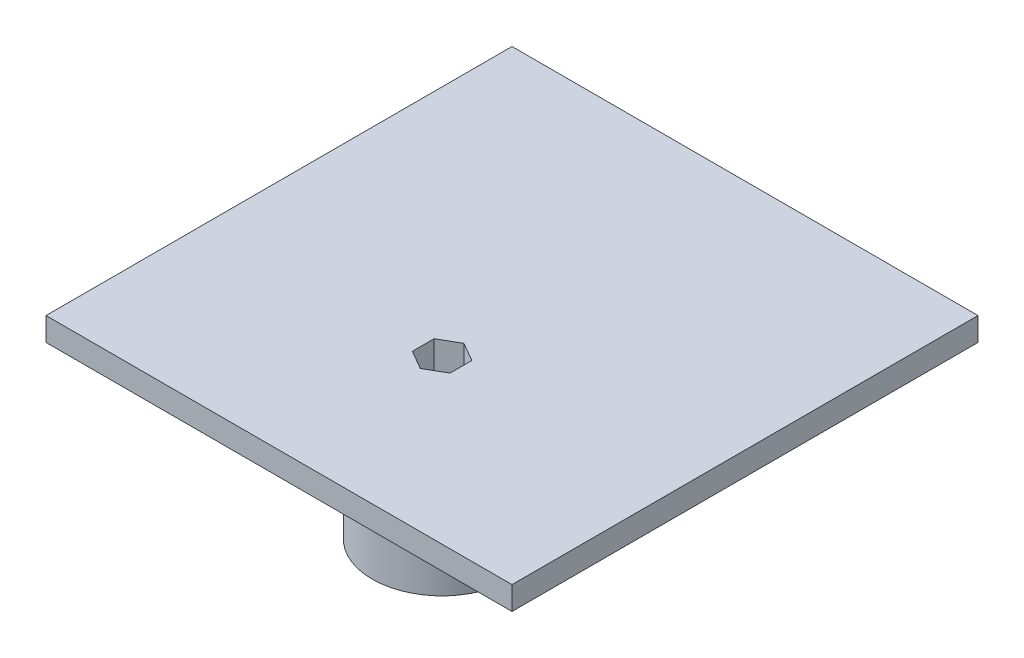
SolidWorks part; units mm, degrees
ref_plane "Plan de face" through (0, 0, 0) normal (0, 0, 1) x (1, 0, 0)
ref_plane "Plan de dessus" through (0, 0, 0) normal (0, 1, 0) x (1, 0, 0)
ref_plane "Plan de droite" through (0, 0, 0) normal (1, 0, 0) x (0, 0, -1)
sketch "Esquisse1" plane through (0, 0, 0) normal (0, 1, 0) x (1, 0, 0)
  line L0 (0, 50) -> (0, -11.7582) construction
  line L1 (50, 50) -> (-50, 50)
  line L2 (50, 50) -> (50, -50)
  line L3 (50, -50) -> (-50, -50)
  line L4 (-50, 50) -> (-50, -50)
  line L5 (50, 50) -> (-50, -50) construction
  line L6 (50, -50) -> (-50, 50) construction
  circle A0 centre (0, -15) radius 2.75
  point P0 (0, 0)
  point P12 (2.7561, -16.0343)
  dimension "D3" = 5.5
  dimension "D1" = 100
  dimension "D2" = 100
  dimension "D4" = 35
  dimension "D5" = 50
extrude "Boss.-Extru.1" add sketch "Esquisse1" along normal blind 5
sketch "Esquisse2" plane through (0, 0, 0) normal (0, -1, 0) x (1, 0, 0)
  line L0 (0, -12.839) -> (0, 22.8722) construction
  line L1 (-37.865, 15) -> (24.9696, 15) construction
  line L2 (-50, -1.5) -> (50, -1.5) construction
  line L3 (-15, 15) -> (-15, -1.5)
  line L4 (-50, 50) -> (-50, -50)
  line L5 (-50, -50) -> (50, -50)
  line L6 (50, -50) -> (50, 50)
  line L7 (50, 50) -> (-50, 50)
  line L8 (-50, 50) -> (-50, -50)
  line L9 (-50, -50) -> (50, -50)
  line L10 (50, -50) -> (50, 50)
  line L11 (50, 50) -> (-50, 50)
  line L12 (15, 15) -> (15, -1.5)
  line L13 (15, -1.5) -> (-15, -1.5)
  arc A0 (-15, 15) -> (15, 15) centre (0, 15) cw
  circle A1 centre (0, 15) radius 2.75 construction
  circle A2 centre (0, 15) radius 2.75
  circle M11 centre (0, 15) radius 2.75
  dimension "D2" = 30
  dimension "D3" = 16.5
  dimension "D1" = 0
extrude "Boss.-Extru.2" add sketch "Esquisse2" along normal blind 29 contours A0 L3 L13 L12 M11 region at (0, 0, 29.565)
sketch "Esquisse3" plane through (0, 0, 0) normal (0, -1, 0) x (1, 0, 0)
  line L0 (-15, -1.5) -> (-15, -45)
  line L1 (-15, -45) -> (15, -45)
  line L2 (15, -45) -> (15, -1.5)
  line L4 (-50, 50) -> (-50, -50)
  line L5 (-50, -50) -> (50, -50)
  line L6 (50, -50) -> (50, 50)
  line L7 (50, 50) -> (-50, 50)
  line L8 (-50, 50) -> (-50, -50)
  line L9 (-50, -50) -> (50, -50)
  line L10 (50, -50) -> (50, 50)
  line L11 (50, 50) -> (-50, 50)
  line M13 (15, -1.5) -> (-15, -1.5)
  dimension "D2" = 5
  dimension "D1" = 0
extrude "Boss.-Extru.3" add sketch "Esquisse3" along normal blind 29 contours L1 L2 L0 M13 region at (0, 0, -23.25)
chamfer "Chanfrein1" distance 29 distance2 45.5 1 edges at (0, -29, -45) first distance on face at (0, -14.5, -45)
sketch "Esquisse4" plane through (0, 5, 0) normal (0, 1, 0) x (1, 0, 0)
  line L0 (0, 0) -> (0, -31.9898) construction
  line L1 (0, -10.3235) -> (-4.05, -12.6617)
  line L2 (-4.05, -12.6617) -> (-4.05, -17.3383)
  line L3 (-4.05, -17.3383) -> (0, -19.6765)
  line L4 (-50, 50) -> (-50, -50)
  line L5 (-50, -50) -> (50, -50)
  line L6 (50, -50) -> (50, 50)
  line L7 (50, 50) -> (-50, 50)
  line L8 (-50, 50) -> (-50, -50)
  line L9 (-50, -50) -> (50, -50)
  line L10 (50, -50) -> (50, 50)
  line L11 (50, 50) -> (-50, 50)
  line L12 (0, -19.6765) -> (4.05, -17.3383)
  line L13 (4.05, -17.3383) -> (4.05, -12.6617)
  line L14 (4.05, -12.6617) -> (0, -10.3235)
  circle A0 centre (0, -15) radius 2.75 construction
  circle A1 centre (0, -15) radius 2.75
  circle A2 centre (0, -15) radius 4.05 construction
  circle M12 centre (0, -15) radius 2.75
  dimension "D2" = 8.1
  dimension "D1" = 0
extrude "Enlèv. mat.-Extru.1" cut sketch "Esquisse4" against normal blind 30 contours L13 L14 L1 L2 L3 L12 M12 region at (1.9631, 5, 11.5998)
sketch "Esquisse7" plane through (0, 0, 0) normal (0, 0, 1) x (1, 0, 0)
  line L0 (-10, 0) -> (-10, -29)
  line L1 (10, 0) -> (10, -29)
  line L2 (0, 0) -> (0, -29) construction
  line L4 (15, 0) -> (-15, 0)
  line L5 (-15, 0) -> (-15, -29)
  line L6 (-15, -29) -> (15, -29)
  line L7 (15, -29) -> (15, 0)
  line L8 (15, 0) -> (-15, 0)
  line L9 (-15, 0) -> (-15, -29)
  line L10 (-15, -29) -> (15, -29)
  line L11 (15, -29) -> (15, 0)
  dimension "D2" = 20
  dimension "D1" = 0
extrude "Enlèv. mat.-Extru.2" cut sketch "Esquisse7" against normal through all contours L2 L8 L0 L10 | L8 L2 L10 L1 region at (-5, -14.5, 0) region at (5, -14.5, 0)
